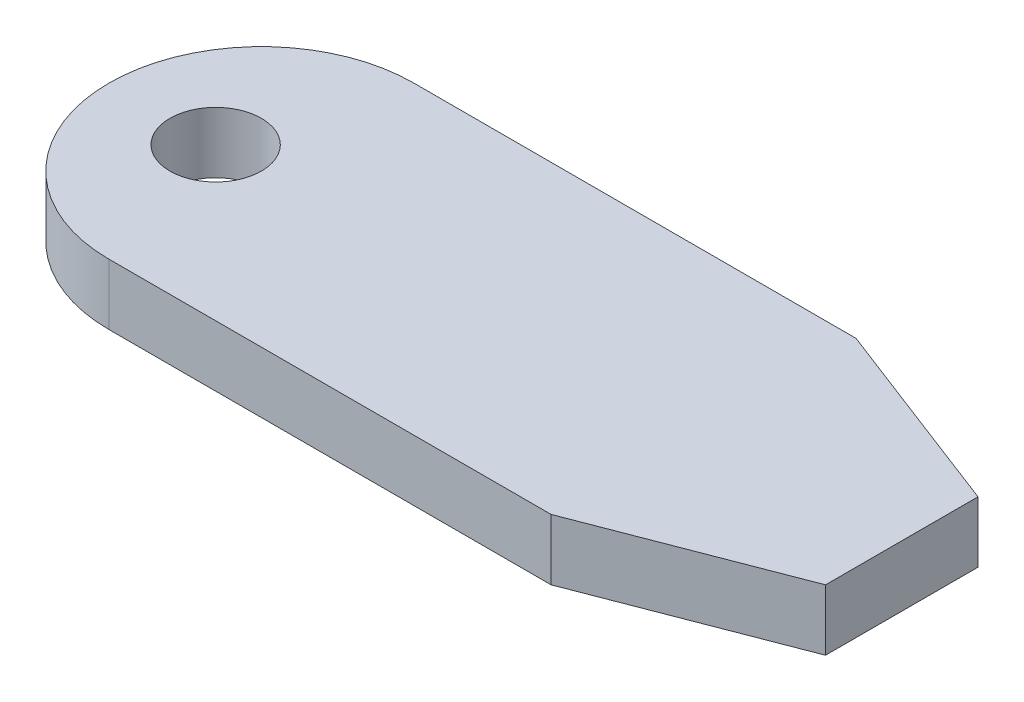
SolidWorks part; units mm, degrees
ref_plane "Alzado" through (0, 0, 0) normal (0, 0, 1) x (1, 0, 0)
ref_plane "Planta" through (0, 0, 0) normal (0, 1, 0) x (1, 0, 0)
ref_plane "Vista lateral" through (0, 0, 0) normal (1, 0, 0) x (0, 0, -1)
sketch "Croquis1" plane through (0, 0, 0) normal (0, 1, 0) x (1, 0, 0)
  line L0 (0, 0) -> (0, 26.7478) construction
  line L1 (0, 0) -> (43.7168, 0) construction
  line L2 (-13, 0) -> (-13, 5)
  line L3 (-13, 5) -> (0, 5)
  line L4 (0, 5) -> (6.5, 5)
  line L5 (13, 2.5) -> (13, 0)
  line L6 (13, 0) -> (13, -2.5)
  line L7 (6.5, -5) -> (0, -5)
  line L8 (0, -5) -> (-13, -5)
  line L9 (-13, -5) -> (-13, 0)
  line L10 (13, 2.5) -> (6.5, 5)
  line L11 (13, -2.5) -> (6.5, -5)
  circle A0 centre (-9.5, 0) radius 1.5
  dimension "D5" = 3.5
  dimension "D1" = 13
extrude "Saliente-Extruir1" add sketch "Croquis1" along normal blind 2
fillet "Redondeo1" radius 5 2 edges at (-13, 1, 5) (-13, 1, -5)
